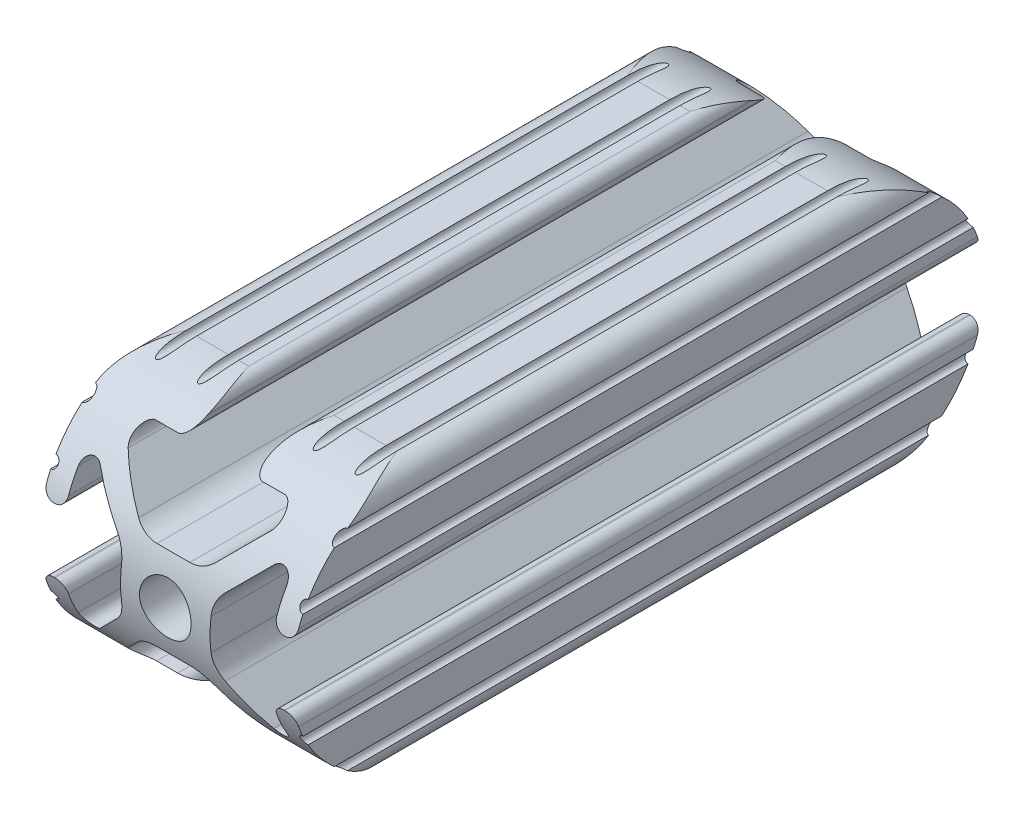
SolidWorks part; units mm, degrees
ref_plane "Front Plane" through (0, 0, 0) normal (0, 0, 1) x (1, 0, 0)
ref_plane "Top Plane" through (0, 0, 0) normal (0, 1, 0) x (1, 0, 0)
ref_plane "Right Plane" through (0, 0, 0) normal (1, 0, 0) x (0, 0, -1)
sketch "Sketch1" plane through (0, 0, 0) normal (0, 0, 1) x (1, 0, 0)
  line L88 (-7.1797, -8.6452) -> (-3.9523, -5.4237)
  line L89 (-1.7093, -4.4958) -> (1.7093, -4.4958)
  line L90 (3.9523, -5.4237) -> (7.1797, -8.6452)
  line L91 (6.4164, -10.4902) -> (4.2875, -10.4902)
  line L92 (3.2385, -11.5392) -> (3.2385, -11.651)
  line L93 (4.2875, -12.7) -> (5.3171, -12.7)
  line L94 (6.3331, -12.7) -> (9.5504, -12.7)
  line L95 (12.7, -9.5504) -> (12.7, -6.3331)
  line L96 (12.7, -5.3171) -> (12.7, -4.2875)
  line L97 (11.651, -3.2385) -> (11.5392, -3.2385)
  line L98 (10.4902, -4.2875) -> (10.4902, -6.4021)
  line L99 (8.7371, -7.1294) -> (5.441, -3.8408)
  line L100 (4.5085, -1.5932) -> (4.5085, 1.5932)
  line L101 (5.441, 3.8408) -> (8.7371, 7.1294)
  line L102 (10.4902, 6.4021) -> (10.4902, 4.2875)
  line L103 (11.5392, 3.2385) -> (11.651, 3.2385)
  line L104 (12.7, 4.2875) -> (12.7, 5.3171)
  line L105 (12.7, 6.3331) -> (12.7, 9.5504)
  line L106 (9.5504, 12.7) -> (6.3331, 12.7)
  line L107 (5.3171, 12.7) -> (4.2875, 12.7)
  line L108 (3.2385, 11.651) -> (3.2385, 11.5392)
  line L109 (4.2875, 10.4902) -> (6.4768, 10.4902)
  line L110 (7.207, 8.7244) -> (3.8983, 5.4232)
  line L111 (1.6558, 4.4958) -> (-1.6558, 4.4958)
  line L112 (-3.8983, 5.4232) -> (-7.207, 8.7244)
  line L113 (-6.4768, 10.4902) -> (-4.2875, 10.4902)
  line L114 (-3.2385, 11.5392) -> (-3.2385, 11.651)
  line L115 (-4.2875, 12.7) -> (-5.3171, 12.7)
  line L116 (-6.3331, 12.7) -> (-9.5504, 12.7)
  line L117 (-12.7, 9.5504) -> (-12.7, 6.3331)
  line L118 (-12.7, 5.3171) -> (-12.7, 4.2875)
  line L119 (-11.651, 3.2385) -> (-11.5392, 3.2385)
  line L120 (-10.4902, 4.2875) -> (-10.4902, 6.4021)
  line L121 (-8.7371, 7.1294) -> (-5.441, 3.8408)
  line L122 (-4.5085, 1.5932) -> (-4.5085, -1.5932)
  line L123 (-5.441, -3.8408) -> (-8.7371, -7.1294)
  line L124 (-10.4902, -6.4021) -> (-10.4902, -4.2875)
  line L125 (-11.5392, -3.2385) -> (-11.651, -3.2385)
  line L126 (-12.7, -4.2875) -> (-12.7, -5.3171)
  line L127 (-12.7, -6.3331) -> (-12.7, -9.5504)
  line L128 (-9.5504, -12.7) -> (-6.3331, -12.7)
  line L129 (-5.3171, -12.7) -> (-4.2875, -12.7)
  line L130 (-3.2385, -11.651) -> (-3.2385, -11.5392)
  line L131 (-4.2875, -10.4902) -> (-6.4164, -10.4902)
  circle A1 centre (0, 0) radius 2.6035
  arc A104 (-7.1797, -8.6452) -> (-6.4164, -10.4902) centre (-6.4164, -9.4098) ccw
  arc A105 (-1.7093, -4.4958) -> (-3.9523, -5.4237) centre (-1.7093, -7.6708) ccw
  arc A106 (3.9523, -5.4237) -> (1.7093, -4.4958) centre (1.7093, -7.6708) ccw
  arc A107 (6.4164, -10.4902) -> (7.1797, -8.6452) centre (6.4164, -9.4098) ccw
  arc A108 (4.2875, -10.4902) -> (3.2385, -11.5392) centre (4.2875, -11.5392) ccw
  arc A109 (3.2385, -11.651) -> (4.2875, -12.7) centre (4.2875, -11.651) ccw
  arc A110 (6.3331, -12.7) -> (5.3171, -12.7) centre (5.8251, -12.7) ccw
  arc A111 (10.5664, -12.6998) -> (9.5504, -12.7) centre (10.0584, -12.7) ccw
  arc A112 (10.5664, -12.6998) -> (12.6998, -10.5664) centre (10.5918, -10.5918) ccw
  arc A113 (12.7, -9.5504) -> (12.6998, -10.5664) centre (12.7, -10.0584) ccw
  arc A114 (12.7, -5.3171) -> (12.7, -6.3331) centre (12.7, -5.8251) ccw
  arc A115 (12.7, -4.2875) -> (11.651, -3.2385) centre (11.651, -4.2875) ccw
  arc A116 (11.5392, -3.2385) -> (10.4902, -4.2875) centre (11.5392, -4.2875) ccw
  arc A117 (8.7371, -7.1294) -> (10.4902, -6.4021) centre (9.4628, -6.4021) ccw
  arc A118 (4.5085, -1.5932) -> (5.441, -3.8408) centre (7.6835, -1.5932) ccw
  arc A119 (5.441, 3.8408) -> (4.5085, 1.5932) centre (7.6835, 1.5932) ccw
  arc A120 (10.4902, 6.4021) -> (8.7371, 7.1294) centre (9.4628, 6.4021) ccw
  arc A121 (10.4902, 4.2875) -> (11.5392, 3.2385) centre (11.5392, 4.2875) ccw
  arc A122 (11.651, 3.2385) -> (12.7, 4.2875) centre (11.651, 4.2875) ccw
  arc A123 (12.7, 6.3331) -> (12.7, 5.3171) centre (12.7, 5.8251) ccw
  arc A124 (12.6998, 10.5664) -> (12.7, 9.5504) centre (12.7, 10.0584) ccw
  arc A125 (12.6998, 10.5664) -> (10.5664, 12.6998) centre (10.5918, 10.5918) ccw
  arc A126 (9.5504, 12.7) -> (10.5664, 12.6998) centre (10.0584, 12.7) ccw
  arc A127 (5.3171, 12.7) -> (6.3331, 12.7) centre (5.8251, 12.7) ccw
  arc A128 (4.2875, 12.7) -> (3.2385, 11.651) centre (4.2875, 11.651) ccw
  arc A129 (3.2385, 11.5392) -> (4.2875, 10.4902) centre (4.2875, 11.5392) ccw
  arc A130 (7.207, 8.7244) -> (6.4768, 10.4902) centre (6.4768, 9.4563) ccw
  arc A131 (1.6558, 4.4958) -> (3.8983, 5.4232) centre (1.6558, 7.6708) ccw
  arc A132 (-3.8983, 5.4232) -> (-1.6558, 4.4958) centre (-1.6558, 7.6708) ccw
  arc A133 (-6.4768, 10.4902) -> (-7.207, 8.7244) centre (-6.4768, 9.4563) ccw
  arc A134 (-4.2875, 10.4902) -> (-3.2385, 11.5392) centre (-4.2875, 11.5392) ccw
  arc A135 (-3.2385, 11.651) -> (-4.2875, 12.7) centre (-4.2875, 11.651) ccw
  arc A136 (-6.3331, 12.7) -> (-5.3171, 12.7) centre (-5.8251, 12.7) ccw
  arc A137 (-10.5664, 12.6998) -> (-9.5504, 12.7) centre (-10.0584, 12.7) ccw
  arc A138 (-10.5664, 12.6998) -> (-12.6998, 10.5664) centre (-10.5918, 10.5918) ccw
  arc A139 (-12.7, 9.5504) -> (-12.6998, 10.5664) centre (-12.7, 10.0584) ccw
  arc A140 (-12.7, 5.3171) -> (-12.7, 6.3331) centre (-12.7, 5.8251) ccw
  arc A141 (-12.7, 4.2875) -> (-11.651, 3.2385) centre (-11.651, 4.2875) ccw
  arc A142 (-11.5392, 3.2385) -> (-10.4902, 4.2875) centre (-11.5392, 4.2875) ccw
  arc A143 (-8.7371, 7.1294) -> (-10.4902, 6.4021) centre (-9.4628, 6.4021) ccw
  arc A144 (-4.5085, 1.5932) -> (-5.441, 3.8408) centre (-7.6835, 1.5932) ccw
  arc A145 (-5.441, -3.8408) -> (-4.5085, -1.5932) centre (-7.6835, -1.5932) ccw
  arc A146 (-10.4902, -6.4021) -> (-8.7371, -7.1294) centre (-9.4628, -6.4021) ccw
  arc A147 (-10.4902, -4.2875) -> (-11.5392, -3.2385) centre (-11.5392, -4.2875) ccw
  arc A148 (-11.651, -3.2385) -> (-12.7, -4.2875) centre (-11.651, -4.2875) ccw
  arc A149 (-12.7, -6.3331) -> (-12.7, -5.3171) centre (-12.7, -5.8251) ccw
  arc A150 (-12.6998, -10.5664) -> (-12.7, -9.5504) centre (-12.7, -10.0584) ccw
  arc A151 (-12.6998, -10.5664) -> (-10.5664, -12.6998) centre (-10.5918, -10.5918) ccw
  arc A152 (-9.5504, -12.7) -> (-10.5664, -12.6998) centre (-10.0584, -12.7) ccw
  arc A153 (-5.3171, -12.7) -> (-6.3331, -12.7) centre (-5.8251, -12.7) ccw
  arc A154 (-4.2875, -12.7) -> (-3.2385, -11.651) centre (-4.2875, -11.651) ccw
  arc A155 (-3.2385, -11.5392) -> (-4.2875, -10.4902) centre (-4.2875, -11.5392) ccw
extrude "Boss-Extrude1" add sketch "Sketch1" along normal mid plane 69.85
sketch "Sketch2" plane through (12.7, 0, 0) normal (1, 0, 0) x (0, 0, -1)
  line L0 (-34.925, 0) -> (34.925, 0) construction
  line L1 (34.925, -12.7) -> (-34.925, -12.7)
  line L2 (34.925, -12.7) -> (34.925, 12.7)
  line L3 (34.925, 12.7) -> (-34.925, 12.7)
  line L4 (-34.925, -12.7) -> (-34.925, 12.7)
  line L5 (34.925, -12.7) -> (-34.925, 12.7) construction
  line L6 (34.925, 12.7) -> (-34.925, -12.7) construction
  circle A0 centre (-22.225, 0) radius 12.7
  circle A1 centre (22.225, 0) radius 12.7
  point P0 (0, 0)
  line M7 (34.925, -9.5504) -> (34.925, -6.3331)
  line M8 (34.925, -6.3331) -> (-34.925, -6.3331)
  line M9 (-34.925, -6.3331) -> (-34.925, -9.5504)
  line M10 (-34.925, -9.5504) -> (34.925, -9.5504)
extrude "Cut-Extrude1" cut sketch "Sketch2" against normal through all contours A0 L3 L4 | A0 L4 M8 | A0 M8 M9 M10 | A0 L4 L1 M10 | A1 L1 L2 M10 | A1 M10 M7 M8 | A1 L2 M8 | A1 L2 L3 region at (12.7, -11.3727, -31.1706) region at (12.7, -8.1865, -33.3938) region at (12.7, -11.3727, 31.1706) region at (12.7, -4.7717, -34.4239) region at (12.7, -8.1865, 33.3938) region at (12.7, 9.8632, -32.0882) region at (12.7, -4.7717, 34.4239) region at (12.7, 9.8632, 32.0882)
